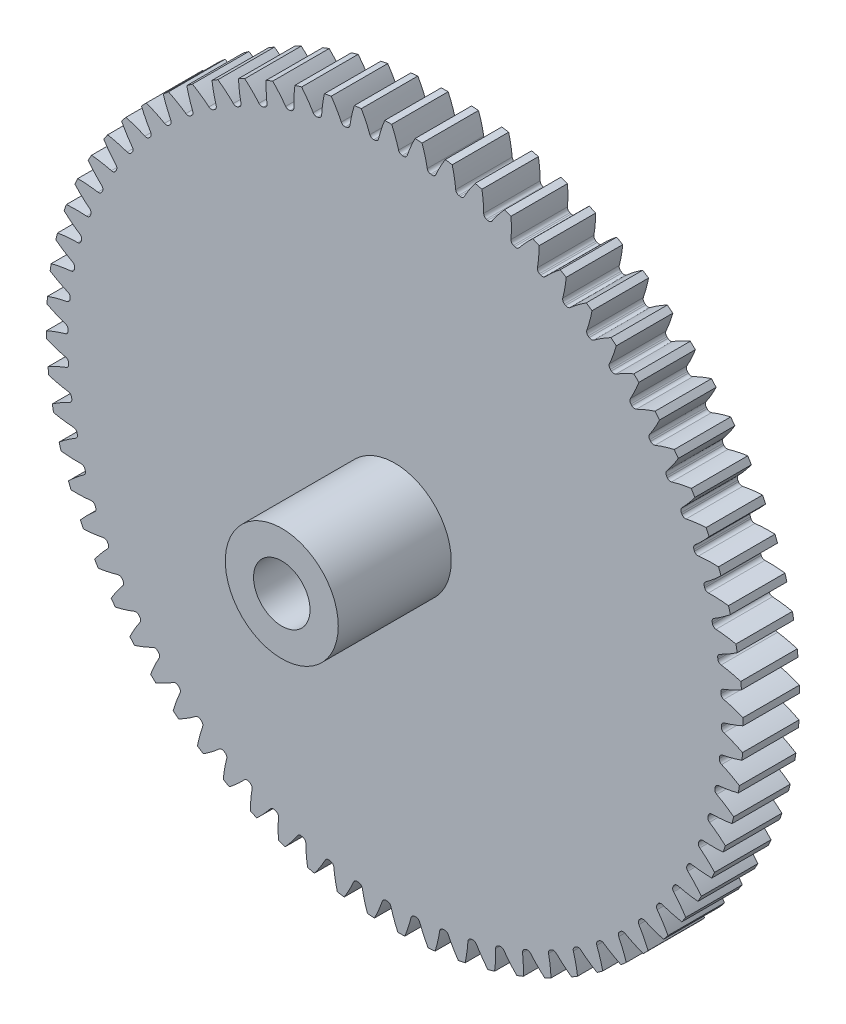
SolidWorks part; units mm, degrees
ref_plane "Front" through (0, 0, 0) normal (0, 0, 1) x (1, 0, 0)
ref_plane "Top" through (0, 0, 0) normal (0, 1, 0) x (1, 0, 0)
ref_plane "Right" through (0, 0, 0) normal (1, 0, 0) x (0, 0, -1)
sketch "Sketch3" plane through (0, 0, 0) normal (0, 0, 1) x (1, 0, 0)
  circle A0 centre (0, 0) radius 19.5792
  dimension "od" = 39.1583
extrude "gearBody" add sketch "Sketch3" along normal blind 3.175
sketch "Sketch2" plane through (0, 0, 0) normal (0, 0, 1) x (1, 0, 0)
  line L0 (0, 0) -> (16.5385, 6.8505) construction
  line L1 (22.4374, -3.832) -> (0, 0) construction
  line L2 (0, 0) -> (36.3143, 0) construction
  line L3 (19.05, -0.043) -> (19.0287, -0.9002) construction
  line L5 (19.0393, -0.4716) -> (0, 0) construction
  line L7 (0, 0) -> (17.9011, 0) construction
  arc A0 (17.8975, -0.3593) -> (17.8934, -0.5273) centre (0, 0) ccw construction
  arc A1 (19.5784, 0.1732) -> (19.5458, -1.1423) centre (0, 0) ccw construction
  arc A2 (19.05, -0.043) -> (19.0287, -0.9002) centre (0, 0) ccw construction
  arc A3 (18.3576, -0.4933) -> (18.3595, -0.4162) centre (0, 0) ccw
  arc A4 (22.4374, -3.832) -> (18.5039, -0.7023) centre (16.179, -7.6609) ccw
  arc A5 (22.4374, -3.832) -> (22.5996, 2.7164) centre (0, 0) ccw
  arc A6 (22.5996, 2.7164) -> (18.516, -0.2147) centre (16.5385, 6.8505) cw
  arc A7 (18.3595, -0.4162) -> (18.516, -0.2147) centre (18.5737, -0.4211) cw
  arc A8 (18.5039, -0.7023) -> (18.3576, -0.4933) centre (18.5718, -0.499) cw
  point P6 (22.5996, 2.7164)
  point P22 (22.4374, -3.832)
  dimension "baseDia" = 35.8023
  dimension "od" = 39.1583
  dimension "pd" = 38.1
  dimension "rd" = 36.7284
  dimension "rFillet" = 0.2143
  dimension "pointX" = 22.5996
  dimension "pointY" = 2.7164
  dimension "CTT" = 0.8573
  dimension "flankCenterAngle" = 22.5
extrude "toothCut" cut sketch "Sketch2" along normal through all
pattern_circular "CirPattern1" count 72 over 360 about axis through (0, 0, 3.175) along (0, 0, -1) of "toothCut"
ref_axis "toothSpace" through (0, 0, 0) along (0.9997, -0.0248, 0)
ref_axis "Axis2" through (19.5334, -1.3382, 0) along (-0.9977, 0.0683, 0)
sketch "hub1Dia" plane through (0, 0, 0) normal (0, 0, -1) x (-1, 0, 0)
  circle A0 centre (0, 0) radius 12.7
  dimension "hub1Dia" = 25.4
sketch "hub2Dia" plane through (0, 0, 3.175) normal (0, 0, 1) x (1, 0, 0)
  circle A0 centre (0, 0) radius 12.7
  dimension "hub2dia" = 25.4
sketch "boreDia" plane through (0, 0, 0) normal (0, 0, 1) x (1, 0, 0)
  circle A0 centre (0, 0) radius 3.175
  dimension "boreDia" = 6.35
extrude "bore" cut sketch "boreDia" against normal mid plane 25400
sketch "kwy1sketch" plane through (0, 0, 0) normal (0, 0, 1) x (1, 0, 0)
  line L0 (-5.3262, 0.2871) -> (0, 0) construction
  line L1 (29.2172, 11.1434) -> (27.8499, -14.2197)
  line L2 (27.8499, -14.2197) -> (-3.854, -12.5107)
  line L3 (29.2172, 11.1434) -> (-2.4868, 12.8525)
  line L4 (-3.854, -12.5107) -> (0, 0)
  line L5 (0, 0) -> (-2.4868, 12.8525)
  line L6 (0, 0) -> (18.3586, -0.4548) construction
  line L7 (28.5336, -1.5382) -> (0, 0) construction
  arc A7 (18.3576, -0.4933) -> (18.3595, -0.4162) centre (0, 0) ccw construction
  point P9 (28.5336, -1.5382)
  point P13 (-0.8885, 0.0479)
  dimension "kwy1width" = 25.4
  dimension "kwy1depth" = 28.575
  dimension "kwy1angle" = 1.667
  dimension "kwy1Depth2" = 31.75
sketch "kwy2sketch" plane through (0, 0, 0) normal (0, 0, 1) x (1, 0, 0)
  line L0 (18.3586, -0.4548) -> (0, 0) construction
  line L1 (0, 0) -> (-2.7429, -2.4623) construction
  line L2 (12.7801, 28.5393) -> (29.7478, 9.638)
  line L3 (29.7478, 9.638) -> (6.1212, -11.5716)
  line L4 (12.7801, 28.5393) -> (-10.8465, 7.3297)
  line L5 (6.1212, -11.5716) -> (0, 0)
  line L6 (0, 0) -> (-10.8465, 7.3297)
  arc A2 (18.3576, -0.4933) -> (18.3595, -0.4162) centre (0, 0) ccw construction
  point P10 (21.2639, 19.0886)
  dimension "kwy2angle" = 43.333
  dimension "kwy2Width" = 25.4
  dimension "kwy2depth" = 28.575
  dimension "kwy2Depth2" = 31.75
sketch "kwy3sketch" plane through (0, 0, 0) normal (0, 0, 1) x (1, 0, 0)
  line L0 (18.3586, -0.4548) -> (0, 0) construction
  line L1 (0, 0) -> (-0.1435, -2.6627) construction
  line L2 (-11.1434, 29.2172) -> (14.2197, 27.8499)
  line L3 (14.2197, 27.8499) -> (12.5107, -3.854)
  line L4 (-11.1434, 29.2172) -> (-12.8525, -2.4868)
  line L5 (12.5107, -3.854) -> (0, 0)
  line L6 (-12.8525, -2.4868) -> (0, 0)
  point P10 (1.5382, 28.5336)
  dimension "kwy3angle" = 88.333
  dimension "kwy3depth" = 28.575
  dimension "kwy3width" = 25.4
  dimension "kwy3Depth2" = 31.75
sketch "kwy4sketch" plane through (0, 0, 0) normal (0, 0, 1) x (1, 0, 0)
  line L0 (18.3586, -0.4548) -> (0, 0) construction
  line L1 (0, 0) -> (1.3928, -1.5516) construction
  line L2 (-9.638, 29.7478) -> (-28.5393, 12.7801)
  line L3 (-28.5393, 12.7801) -> (-7.3297, -10.8465)
  line L4 (-7.3297, -10.8465) -> (0, 0)
  line L5 (11.5716, 6.1212) -> (0, 0)
  line L6 (-9.638, 29.7478) -> (11.5716, 6.1212)
  point P15 (-19.0886, 21.2639)
  dimension "kwy4angle" = 133.333
  dimension "kwy4depth" = 28.575
  dimension "kwy4width" = 25.4
  dimension "kwy4Depth2" = 31.75
sketch "kwy5sketch" plane through (0, 0, 0) normal (0, 0, 1) x (1, 0, 0)
  line L0 (18.3586, -0.4548) -> (0, 0) construction
  line L1 (0, 0) -> (1.7881, -0.0964) construction
  line L2 (-27.8499, 14.2197) -> (-29.2172, -11.1434)
  line L3 (-29.2172, -11.1434) -> (2.4868, -12.8525)
  line L4 (-27.8499, 14.2197) -> (3.854, 12.5107)
  line L5 (2.4868, -12.8525) -> (0, 0)
  line L6 (3.854, 12.5107) -> (0, 0)
  point P10 (-28.5336, 1.5382)
  dimension "kwy5width" = 25.4
  dimension "kwy5depth" = 28.575
  dimension "kwy5angle" = 178.333
  dimension "kwy5Depth2" = 31.75
sketch "kwy6sketch" plane through (0, 0, 0) normal (0, 0, 1) x (1, 0, 0)
  line L0 (18.3586, -0.4548) -> (0, 0) construction
  line L1 (0, 0) -> (1.3315, 1.1953) construction
  line L2 (-29.7478, -9.638) -> (-12.7801, -28.5393)
  line L3 (-12.7801, -28.5393) -> (10.8465, -7.3297)
  line L4 (-29.7478, -9.638) -> (-6.1212, 11.5716)
  line L5 (10.8465, -7.3297) -> (0, 0)
  line L6 (-6.1212, 11.5716) -> (0, 0)
  point P10 (-21.2639, -19.0886)
  dimension "kwy6angle" = 223.333
  dimension "kwy6width" = 25.4
  dimension "kwy6depth" = 28.575
  dimension "kwy6Depth2" = 31.75
sketch "kwy7sketch" plane through (0, 0, 0) normal (0, 0, 1) x (1, 0, 0)
  line L0 (18.3586, -0.4548) -> (0, 0) construction
  line L1 (0, 0) -> (0.1079, 2.0017) construction
  line L2 (-14.2197, -27.8499) -> (11.1434, -29.2172)
  line L3 (-14.2197, -27.8499) -> (-12.5107, 3.854)
  line L4 (11.1434, -29.2172) -> (12.8525, 2.4868)
  line L5 (-12.5107, 3.854) -> (0, 0)
  line L6 (12.8525, 2.4868) -> (0, 0)
  point P10 (-1.5382, -28.5336)
  dimension "kwy7angle" = 88.333
  dimension "kwy7width" = 25.4
  dimension "kwy7depth" = 28.575
  dimension "kwy7angle1" = 268.333
  dimension "kwy7Depth2" = 31.75
sketch "kwy8sketch" plane through (0, 0, 0) normal (0, 0, 1) x (1, 0, 0)
  line L0 (18.3586, -0.4548) -> (0, 0) construction
  line L1 (0, 0) -> (-1.1897, 1.3253) construction
  line L2 (9.638, -29.7478) -> (28.5393, -12.7801)
  line L3 (28.5393, -12.7801) -> (7.3297, 10.8465)
  line L4 (9.638, -29.7478) -> (-11.5716, -6.1212)
  line L5 (7.3297, 10.8465) -> (0, 0)
  line L6 (-11.5716, -6.1212) -> (0, 0)
  point P10 (19.0886, -21.2639)
  dimension "kwy8angle" = 313.333
  dimension "kwy8width" = 25.4
  dimension "kwy8depth" = 28.575
  dimension "kwy8Depth2" = 31.75
sketch "centerLine" plane through (0, 0, 0) normal (0, 1, 0) x (1, 0, 0)
  line L0 (0, 36.4807) -> (0, -59.6309) construction
ref_plane "CB1plane" through (0, 0, 0) normal (0, 0, -1) x (-1, 0, 0)
sketch "CB1diameter" plane through (0, 0, 0) normal (0, 0, -1) x (-1, 0, 0)
  circle A0 centre (0, 0) radius 12.7
  dimension "CB1diameter" = 25.4
ref_plane "CB2plane" through (0, 0, 3.175) normal (0, 0, 1) x (1, 0, 0)
sketch "CB2diameter" plane through (0, 0, 3.175) normal (0, 0, 1) x (1, 0, 0)
  circle A0 centre (0, 0) radius 12.7
  dimension "CB2diameter" = 25.4
ref_axis "Axis1" through (0, 0, 50) along (0, 0, -1)
sketch3d "3DSketch1" plane through (0, 0, 0) normal (0, 0, 1) x (1, 0, 0)
sketch "Sketch4" plane through (0, 0, 3.175) normal (0, 0, 1) x (1, 0, 0)
  circle A0 centre (0, 0) radius 3.175
extrude "Boss-Extrude1" add sketch "Sketch4" along normal blind 6.35 separate body
sketch "Sketch5" plane through (0, 0, 9.525) normal (0, 0, 1) x (1, 0, 0)
  circle A0 centre (0, 0) radius 1.5875
extrude "Cut-Extrude1" cut sketch "Sketch5" against normal up to next (6.35 mm away)
